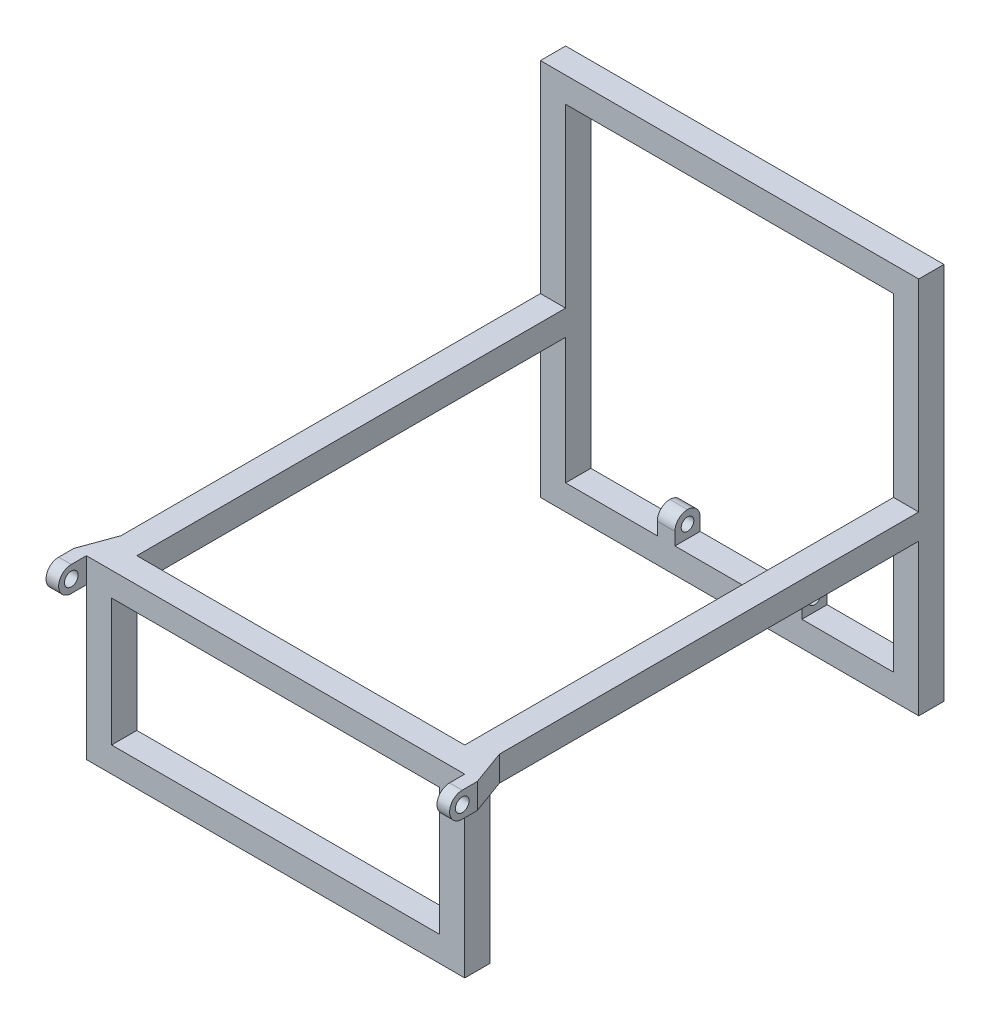
SolidWorks part; units mm, degrees
ref_plane "Alzado" through (0, 0, 0) normal (0, 0, 1) x (1, 0, 0)
ref_plane "Planta" through (0, 0, 0) normal (0, 1, 0) x (1, 0, 0)
ref_plane "Vista lateral" through (0, 0, 0) normal (1, 0, 0) x (0, 0, -1)
sketch "Croquis1" plane through (0, 0, 0) normal (1, 0, 0) x (0, 0, -1)
  line L0 (-100, 700) -> (-100, 1500)
  line L1 (0, 0) -> (-100, 0)
  line L2 (0, 0) -> (0, 1500)
  line L3 (0, 1500) -> (-100, 1500)
  line L4 (-100, 0) -> (-100, 600)
  line L5 (-100, 600) -> (-1800, 600)
  line L6 (0, 600) -> (0, 700)
  line L7 (-100, 700) -> (-1900, 700)
  line L8 (-1900, 600) -> (-1900, 700)
  line L10 (-1900, 600) -> (-1900, 0)
  line L11 (-1900, 0) -> (-1800, 0)
  line L12 (-1800, 600) -> (-1800, 0)
  point P16 (-950, 600)
  point P17 (-50, 0)
  point P18 (-1850, 0)
  dimension "D1" = 100
  dimension "D2" = 1500
  dimension "D3" = 700
  dimension "D4" = 100
  dimension "D5" = 1700
  dimension "D6" = 600
extrude "Saliente-Extruir1" add sketch "Croquis1" against normal mid plane 1500 contours L7 L8 L10 L11 L12 L5 L4 L1 L2 L3 L0
sketch "Croquis3" plane through (0, 0, 0) normal (0, 0, -1) x (-1, 0, 0)
  line L0 (750, 0) -> (750, 1500) construction
  line L1 (750, 0) -> (-750, 0) construction
  line L2 (750, 1500) -> (-750, 1500) construction
  line L8 (-750, 0) -> (-750, 1500) construction
  line L9 (-650, 1400) -> (650, 1400)
  line L10 (-650, 1400) -> (-650, 100)
  line L11 (-650, 100) -> (650, 100)
  line L12 (650, 1400) -> (650, 100)
  dimension "D1" = 100
  dimension "D2" = 100
  dimension "D3" = 100
  dimension "D4" = 100
extrude "Cortar-Extruir4" cut sketch "Croquis3" against normal up to surface (1800 mm away) up to face at (0, 300, 1800)
sketch "Croquis4" plane through (0, 0, 1900) normal (0, 0, 1) x (1, 0, 0)
  line L0 (-750, 700) -> (750, 700) construction
  line L1 (-650, 604.6492) -> (650, 604.6492)
  line L2 (-650, 604.6492) -> (-650, 100)
  line L3 (-650, 100) -> (650, 100)
  line L4 (650, 604.6492) -> (650, 100)
  line L5 (750, 0) -> (750, 700) construction
  line L6 (-750, 0) -> (750, 0) construction
  line L7 (-750, 700) -> (-750, 0) construction
  dimension "D1" = 95.3508
  dimension "D2" = 100
  dimension "D3" = 100
  dimension "D4" = 100
extrude "Cortar-Extruir5" cut sketch "Croquis4" against normal up to next
sketch "Croquis5" plane through (750, 0, 0) normal (1, 0, 0) x (0, 0, -1)
  line L0 (-1960, 600) -> (-1900, 600)
  line L1 (-1900, 0) -> (-1900, 700) construction
  line L2 (-1900, 600) -> (-1900, 700)
  line L4 (-1900, 700) -> (-1960, 700)
  arc A0 (-1960, 700) -> (-1960, 600) centre (-1960, 650) ccw
  circle A1 centre (-1960, 650) radius 27.1847
  dimension "D1" = 60
  dimension "D2" = 100
  dimension "D3" = 54.3694
extrude "Saliente-Extruir2" add sketch "Croquis5" along normal blind 50 separate body
sketch "Croquis6" plane through (0, 700, 0) normal (0, 1, 0) x (1, 0, 0)
  line L0 (750, -1900) -> (800, -1900)
  line L1 (800, -1900) -> (750, -1762.6261)
  line L2 (750, -100) -> (750, -1900) construction
  line L3 (750, -1900) -> (750, -1762.6261)
  dimension "D1" = 70
extrude "Saliente-Extruir3" add sketch "Croquis6" against normal up to surface (100 mm away) up to face at (775, 600, 1930)
sketch "Croquis8" plane through (-750, 0, 0) normal (-1, 0, 0) x (0, 0, 1)
  line L0 (1900, 700) -> (1960, 700)
  line L1 (1900, 600) -> (1960, 600)
  line L2 (1900, 700) -> (1960, 700) construction
  line L3 (1900, 700) -> (1960, 700) construction
  circle A0 centre (1960, 650) radius 27.1845
  arc A1 (1960, 600) -> (1960, 700) centre (1960, 650) ccw
  line M11 (1900, 0) -> (1900, 700)
  dimension "D1" = 54.369
extrude "Saliente-Extruir4" add sketch "Croquis8" along normal blind 50 separate body contours L1 A1 L0 A0 M11
sketch "Croquis9" plane through (0, 700, 0) normal (0, 1, 0) x (1, 0, 0)
  line L0 (-750, -1900) -> (-800, -1900)
  line L1 (-800, -1900) -> (-750, -1762.6261)
  line L2 (-750, -100) -> (-750, -1900) construction
  line L3 (-750, -1762.6261) -> (-750, -1900)
  dimension "D1" = 70
extrude "Saliente-Extruir5" add sketch "Croquis9" against normal up to surface (100 mm away) up to face at (-775, 600, 1930)
sketch "Croquis11" plane through (0, 0, 0) normal (0, 0, -1) x (-1, 0, 0)
  line L0 (-650, 100) -> (650, 100) construction
  line L1 (-286.7, 100) -> (-216.7, 100)
  line L2 (-286.7, 100) -> (-286.7, 200)
  line L3 (-286.7, 200) -> (-216.7, 200)
  line L4 (-216.7, 100) -> (-216.7, 200)
  line L5 (-216.7, 700) -> (-216.7, 800) construction
  line L6 (0, 0) -> (0, 100) construction
  line L7 (286.7, 200) -> (216.7, 200)
  line L8 (216.7, 100) -> (216.7, 200)
  line L9 (286.7, 100) -> (216.7, 100)
  line L10 (286.7, 100) -> (286.7, 200)
  point P8 (-216.7, 750)
  point P9 (-216.7, 150)
  dimension "D1" = 70
  dimension "D2" = 100
extrude "Saliente-Extruir6" add sketch "Croquis11" against normal up to surface (100 mm away) up to face at (0, 325, 100)
fillet "Redondeo1" radius 50 4 edges at (251.7, 200, 100) (251.7, 200, 0) (-251.7, 200, 100) (-251.7, 200, 0)
sketch "Croquis12" plane through (-286.7, 0, 0) normal (-1, 0, 0) x (0, 0, 1)
  circle A0 centre (50, 150) radius 25
  arc A1 (100, 150) -> (50, 200) centre (50, 150) ccw construction
  dimension "D1" = 50
extrude "Cortar-Extruir6" cut sketch "Croquis12" against normal up to surface (573.4 mm away) up to face at (286.7, 144.1421, 50)
